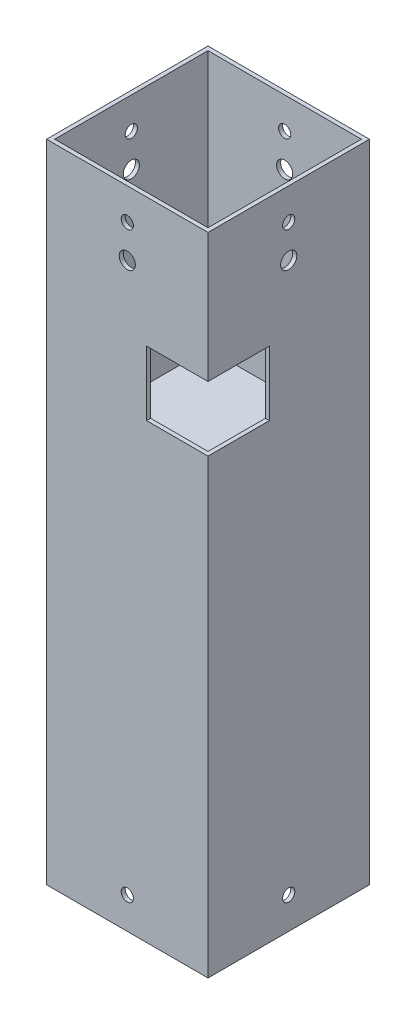
SolidWorks part; units mm, degrees
material "6061 Alloy"
ref_plane "Front Plane" through (0, 0, 0) normal (0, 0, 1) x (1, 0, 0)
ref_plane "Top Plane" through (0, 0, 0) normal (0, 1, 0) x (1, 0, 0)
ref_plane "Right Plane" through (0, 0, 0) normal (1, 0, 0) x (0, 0, -1)
sketch "Sketch1" plane through (0, 0, 0) normal (0, 1, 0) x (1, 0, 0)
  line L1 (-30.1625, 30.1625) -> (30.1625, 30.1625)
  line L2 (-30.1625, 30.1625) -> (-30.1625, -30.1625)
  line L3 (-30.1625, -30.1625) -> (30.1625, -30.1625)
  line L4 (30.1625, 30.1625) -> (30.1625, -30.1625)
  line L5 (-31.75, 31.75) -> (31.75, 31.75)
  line L6 (-31.75, 31.75) -> (-31.75, -31.75)
  line L7 (-31.75, -31.75) -> (31.75, -31.75)
  line L8 (31.75, 31.75) -> (31.75, -31.75)
  point P2 (-31.75, 0)
  point P11 (-30.1625, 0)
  point P12 (0, 30.1625)
  point P13 (0, 31.75)
  dimension "D1" = 60.325
  dimension "1.95" = 60.325
  dimension "2.05" = 63.5
  dimension "D2" = 63.5
extrude "Boss-Extrude1" add sketch "Sketch1" along normal blind 254
ref_plane "Plane1" through (0, 152.4, 0) normal (0, 1, 0) x (1, 0, 0)
sketch "Sketch3" plane through (0, 152.4, 0) normal (0, 1, 0) x (1, 0, 0)
  line L1 (-30.1625, 30.1625) -> (30.1625, 30.1625)
  line L2 (-30.1625, 30.1625) -> (-30.1625, -30.1625)
  line L3 (-30.1625, -30.1625) -> (30.1625, -30.1625)
  line L4 (30.1625, 30.1625) -> (30.1625, -30.1625)
extrude "Boss-Extrude3" add sketch "Sketch3" against normal blind 2.54
sketch "Sketch4" plane through (-30.1625, 0, 0) normal (1, 0, 0) x (0, 0, -1)
  line L0 (-31.75, 254) -> (31.75, 254) construction
  line L1 (31.75, 254) -> (31.75, 0) construction
  circle A0 centre (0, 241.5876) radius 2.4
  dimension "D1" = 4.8
  dimension "D2" = 12.4124
  dimension "D3" = 31.75
extrude "Cut-Extrude1" cut sketch "Sketch4" along normal through all both and the other way through all
sketch "Sketch5" plane through (0, 0, -31.75) normal (0, 0, -1) x (-1, 0, 0)
  line L0 (-31.75, 254) -> (31.75, 254) construction
  line L1 (31.75, 254) -> (31.75, 0) construction
  circle A0 centre (0, 241.5876) radius 2.4
  dimension "D1" = 4.8
  dimension "D2" = 12.4124
  dimension "D3" = 31.75
extrude "Cut-Extrude2" cut sketch "Sketch5" against normal through all
sketch "Sketch6" plane through (31.75, 0, 0) normal (1, 0, 0) x (0, 0, -1)
  line L0 (-31.75, 0) -> (31.75, 0) construction
  line L1 (31.75, 254) -> (31.75, 0) construction
  circle A0 centre (0, 12.4124) radius 2.4
  dimension "D1" = 12.4124
  dimension "D2" = 4.8
  dimension "D3" = 31.75
extrude "Cut-Extrude3" cut sketch "Sketch6" against normal through all both and the other way through all
sketch "Sketch7" plane through (0, 0, -31.75) normal (0, 0, -1) x (-1, 0, 0)
  line L0 (-31.75, 0) -> (31.75, 0) construction
  circle A0 centre (0, 12.4124) radius 2.4
  dimension "D1" = 4.8
  dimension "D2" = 12.4124
  dimension "D3" = 31.75
extrude "Cut-Extrude4" cut sketch "Sketch7" against normal through all both
sketch "Sketch8" plane through (0, 0, -31.75) normal (0, 0, -1) x (-1, 0, 0)
  line L0 (-31.75, 254) -> (31.75, 254) construction
  line L1 (-31.75, 254) -> (-31.75, 0) construction
  circle A0 centre (0, 228.6) radius 3.175
  dimension "D1" = 6.35
  dimension "D2" = 25.4
  dimension "D3" = 31.75
extrude "Cut-Extrude5" cut sketch "Sketch8" against normal through all both and the other way through all
sketch "Sketch9" plane through (31.75, 0, 0) normal (1, 0, 0) x (0, 0, -1)
  line L0 (-31.75, 254) -> (31.75, 254) construction
  line L1 (-31.75, 254) -> (-31.75, 0) construction
  circle A0 centre (0, 228.6) radius 3.175
  dimension "D1" = 6.35
  dimension "D2" = 25.4
  dimension "D3" = 31.75
extrude "Cut-Extrude6" cut sketch "Sketch9" against normal through all both
sketch "Sketch10" plane through (31.75, 0, 0) normal (1, 0, 0) x (0, 0, -1)
  line L0 (-31.75, 254) -> (-31.75, 0) construction
  line L1 (-31.75, 203.2) -> (-7.62, 203.2)
  line L2 (-31.75, 203.2) -> (-31.75, 177.8)
  line L3 (-31.75, 177.8) -> (-7.62, 177.8)
  line L4 (-7.62, 203.2) -> (-7.62, 177.8)
  line L5 (-31.75, 254) -> (31.75, 254) construction
  dimension "D1" = 50.8
  dimension "D2" = 25.4
  dimension "D3" = 24.13
extrude "Cut-Extrude7" cut sketch "Sketch10" against normal blind 24.13
equation "\"1.95@Sketch1\"=2.5-(1/8)"
equation "\"D1@Sketch1\"=\"1.95@Sketch1\""
